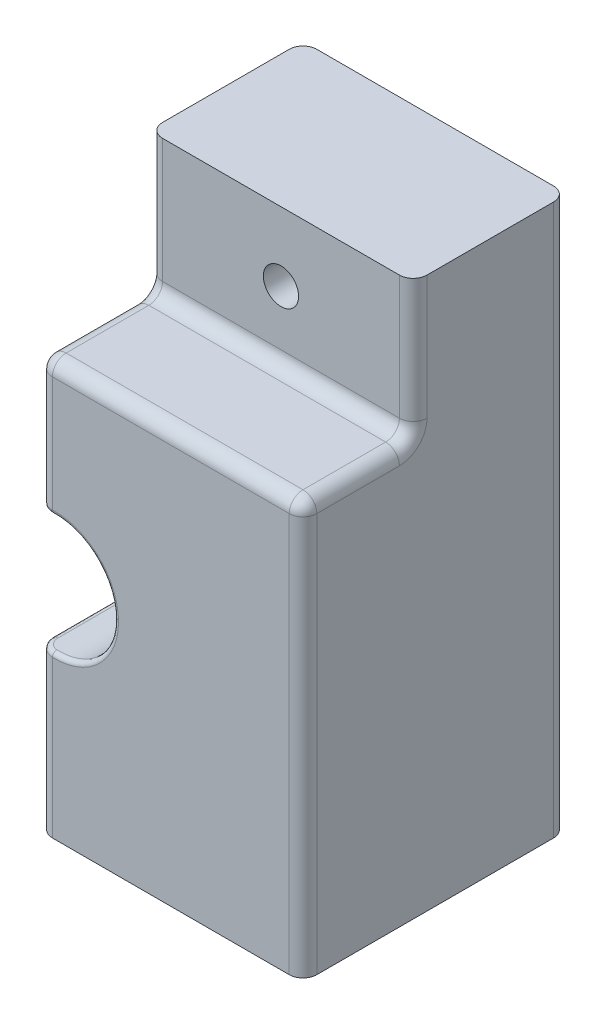
SolidWorks part; units mm, degrees
ref_plane "Front Plane" through (0, 0, 0) normal (0, 0, 1) x (1, 0, 0)
ref_plane "Top Plane" through (0, 0, 0) normal (0, 1, 0) x (1, 0, 0)
ref_plane "Right Plane" through (0, 0, 0) normal (1, 0, 0) x (0, 0, -1)
sketch "Sketch1" plane through (0, 0, 0) normal (0, 1, 0) x (1, 0, 0)
  line L1 (-7.62, -7.62) -> (7.62, -7.62)
  line L2 (-7.62, -7.62) -> (-7.62, 7.62)
  line L3 (-7.62, 7.62) -> (7.62, 7.62)
  line L4 (7.62, -7.62) -> (7.62, 7.62)
  line L5 (-7.62, -7.62) -> (7.62, 7.62) construction
  line L6 (-7.62, 7.62) -> (7.62, -7.62) construction
  point P0 (0, 0)
  dimension "D1" = 15.24
extrude "Boss-Extrude1" add sketch "Sketch1" along normal blind 31.75
fillet "Fillet1" radius 0.7937 4 edges at (-7.62, 15.875, 7.62) (7.62, 15.875, -7.62) (-7.62, 15.875, -7.62) (7.62, 15.875, 7.62)
sketch "Sketch2" plane through (0, 0, 7.62) normal (0, 0, 1) x (1, 0, 0)
  line L0 (-7.62, 31.75) -> (-7.62, 0) construction
  line L1 (-7.62, 31.75) -> (-7.62, 0)
  line L2 (-6.8262, 31.75) -> (6.8263, 31.75) construction
  line L3 (7.62, 31.75) -> (7.62, 0) construction
  line L4 (-7.62, 31.75) -> (7.62, 31.75)
  line L5 (-7.62, 31.75) -> (-7.62, 23.8125)
  line L6 (-7.62, 23.8125) -> (7.62, 23.8125)
  line L7 (7.62, 31.75) -> (7.62, 23.8125)
  arc A0 (-7.62, 9.398) -> (-7.62, 16.002) centre (-6.6954, 12.7) ccw
  line M3 (6.8263, 31.75) -> (-6.8262, 31.75)
  line M16 (-6.8262, 31.75) -> (-6.8262, 0)
  line M17 (6.8263, 0) -> (6.8263, 31.75)
  dimension "D1" = 6.858
  dimension "D2" = 6.604
  dimension "D3" = 19.05
  dimension "D4" = 7.9375
extrude "Cut-Extrude1" cut sketch "Sketch2" against normal through all contours L1 A0 | A0 M16 region at (-7.2207, 12.7, 7.62) region at (-5.3105, 12.7, 7.62)
extrude "Cut-Extrude2" cut sketch "Sketch2<3>" against normal blind 6.35 contours L6 M3 | L1 L6 L4 M16 | L7 L4 L6 M17 region at (-7.2231, 27.7812, 7.62) region at (0, 27.7812, 7.62) region at (7.2231, 27.7812, 7.62)
sketch "Sketch2<3>" plane through (0, 0, 7.62) normal (0, 0, 1) x (1, 0, 0) same geometry as "Sketch2"
sketch "Sketch3" plane through (0, 0, 1.27) normal (0, 0, 1) x (1, 0, 0)
  line L0 (-7.62, 31.75) -> (-7.62, 23.8125) construction
  line L1 (7.62, 31.75) -> (-7.62, 31.75) construction
  point P0 (0, 27.7812)
  point P3 (-7.62, 27.7812)
  point P6 (0, 31.75)
hole_wizard "#4 (0.209) Diameter Hole1" positions "Sketch4" profile "Sketch5" hole size "#4" standard "ANSI Inch"
sketch "Sketch4" plane through (0, 0, 1.27) normal (0, 0, 1) x (1, 0, 0)
  point P0 (0, 27.7812)
sketch "Sketch5" plane through (0, 27.7812, 1.27) normal (1, 0, 0) x (0, -1, 0)
  line L0 (0, 0) -> (0, 6.9605)
  line L1 (0, 6.9605) -> (1.016, 6.35)
  line L2 (1.016, 6.35) -> (1.016, 0)
  line L5 (1.016, 0) -> (0, 0)
  line L10 (0, 6.9605) -> (-1.016, 6.35) construction
  line L11 (0, -6.35) -> (0, 107.95) construction
  dimension "Hole Dia." = 2.032
  dimension "Hole Depth" = 6.35
  dimension "Drill Angle" = 118
sketch "Sketch6" plane through (0, 0, 0) normal (0, -1, 0) x (-1, 0, 0)
  point P0 (0, 0)
hole_wizard "#10 (0.1935) Diameter Hole1" positions "Sketch7" profile "Sketch8" hole size "#10" standard "ANSI Inch"
sketch "Sketch7" plane through (0, 0, 0) normal (0, -1, 0) x (-1, 0, 0)
  point P0 (0, 0)
sketch "Sketch8" plane through (0, 0, 0) normal (1, 0, 0) x (0, 0, -1)
  line L0 (0, 0) -> (0, 7.4183)
  line L1 (0, 7.4183) -> (1.778, 6.35)
  line L2 (1.778, 6.35) -> (1.778, 0)
  line L5 (1.778, 0) -> (0, 0)
  line L10 (0, 7.4183) -> (-1.778, 6.35) construction
  line L11 (0, -6.35) -> (0, 107.95) construction
  dimension "Hole Dia." = 3.556
  dimension "Hole Depth" = 6.35
  dimension "Drill Angle" = 118
fillet "Fillet2" radius 0.7937 8 edges at (7.62, 27.7812, 1.27) (-7.62, 27.7812, 1.27) (0, 23.8125, 7.62) (-7.3875, 23.8125, 7.3875) (-7.62, 23.8125, 4.0481) (0, 23.8125, 1.27) (7.62, 23.8125, 4.0481) (7.3875, 23.8125, 7.3875)
fillet "Fillet3" radius 0.254 8 edges at (-7.3161, 9.3276, -7.4508) (-3.2664, 12.7, -7.62) (-7.4546, 16.0439, -7.3112) (-7.62, 16.002, 0) (-7.3161, 16.0724, 7.4508) (-3.2664, 12.7, 7.62) (-7.4546, 9.3561, 7.3112) (-7.62, 9.398, 0)
